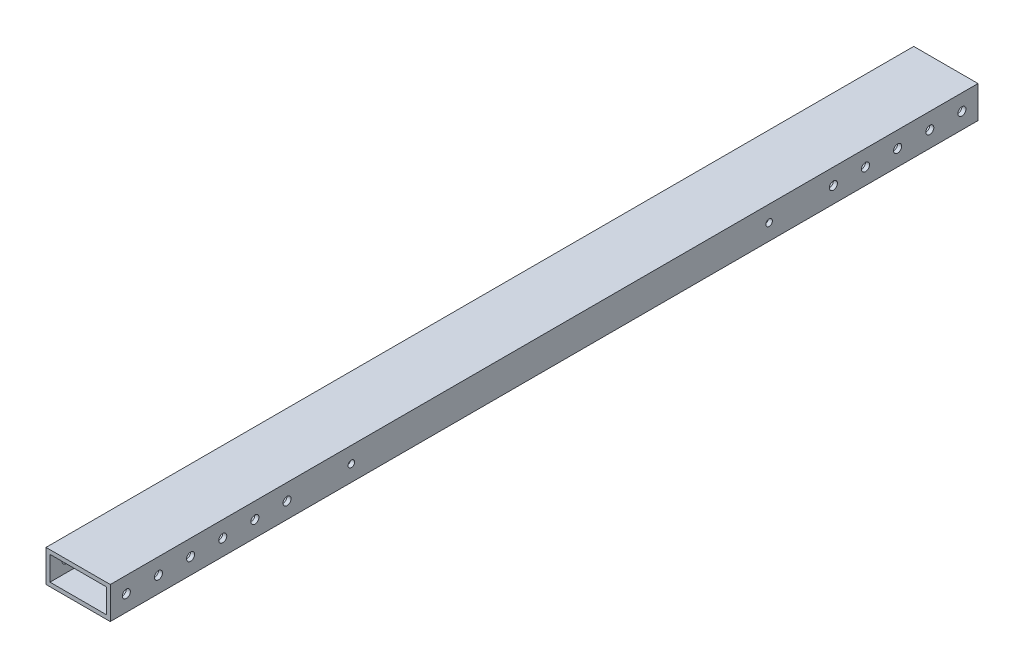
SolidWorks part; units mm, degrees
material "6061 Alloy"
ref_plane "Front Plane" through (0, 0, 0) normal (0, 0, 1) x (1, 0, 0)
ref_plane "Top Plane" through (0, 0, 0) normal (0, 1, 0) x (1, 0, 0)
ref_plane "Right Plane" through (0, 0, 0) normal (1, 0, 0) x (0, 0, -1)
sketch "Sketch1" plane through (0, 0, 0) normal (0, 0, 1) x (1, 0, 0)
  line L0 (-22.225, 9.525) -> (22.225, 9.525)
  line L2 (-25.4, 12.7) -> (25.4, 12.7)
  line L3 (-25.4, 12.7) -> (-25.4, -12.7)
  line L4 (-25.4, -12.7) -> (25.4, -12.7)
  line L5 (25.4, 12.7) -> (25.4, -12.7)
  line L10 (22.225, 9.525) -> (22.225, -9.525)
  line L11 (-22.225, -9.525) -> (22.225, -9.525)
  line L12 (-22.225, 9.525) -> (-22.225, -9.525)
  point P12 (0, 12.7)
  point P14 (25.4, 0)
  dimension "Wall Thickness" = 3.175
  dimension "Outside Width" = 50.8
  dimension "Outside Height" = 25.4
  dimension "Inside Height" = 19.05
  dimension "Inside Width" = 44.45
sketch "Sketch2" plane through (0, 0, 0) normal (1, 0, 0) x (0, 0, -1)
  line L0 (342.9, 0) -> (-342.9, 0)
  point P4 (0, 0)
  point P7 (-342.9, 0)
  point P10 (342.9, 0)
  dimension "Length" = 685.8
sketch "Sketch3" plane through (0, 0, 0) normal (0, 0, 1) x (1, 0, 0)
  line L21 (25.4, 12.7) -> (-25.4, 12.7)
  line L22 (25.4, -12.7) -> (25.4, 12.7)
  line L23 (-25.4, -12.7) -> (25.4, -12.7)
  line L24 (-25.4, 12.7) -> (-25.4, -12.7)
  line L25 (25.4, 12.7) -> (-25.4, 12.7)
  line L26 (25.4, -12.7) -> (25.4, 12.7)
  line L27 (-25.4, -12.7) -> (25.4, -12.7)
  line L28 (-25.4, 12.7) -> (-25.4, -12.7)
  line L29 (22.225, 9.525) -> (-22.225, 9.525)
  line L30 (22.225, -9.525) -> (22.225, 9.525)
  line L31 (-22.225, -9.525) -> (22.225, -9.525)
  line L32 (-22.225, 9.525) -> (-22.225, -9.525)
  line L33 (22.225, 9.525) -> (-22.225, 9.525)
  line L34 (22.225, -9.525) -> (22.225, 9.525)
  line L35 (-22.225, -9.525) -> (22.225, -9.525)
  line L36 (-22.225, 9.525) -> (-22.225, -9.525)
  dimension "D1" = 0
  dimension "D2" = 0
extrude "Boss-Extrude1" add sketch "Sketch3" along normal up to vertex (342.9 mm away) and the other way up to vertex (342.9 mm away) up to point (0, 0, 342.9) other way up to point (0, 0, -342.9)
sketch "Drawing Reference" plane through (0, 0, 0) normal (1, 0, 0) x (0, 0, -1)
  line L0 (-342.9, 0) -> (342.9, 0) construction
  line L1 (0, -12.7) -> (0, 12.7) construction
  line L2 (-342.9, -12.7) -> (342.9, -12.7) construction
  line L5 (-342.9, 12.7) -> (342.9, 12.7) construction
  point P7 (-306.324, 0)
  point P8 (306.324, 0)
  dimension "D1" = 36.576
sketch "Sketch5" plane through (25.4, 0, 0) normal (1, 0, 0) x (0, 0, -1)
  line L0 (-342.9, 0) -> (-279.4, 0)
  line L1 (-342.9, -12.7) -> (-342.9, 12.7) construction
  line L2 (-279.4, 0) -> (-254, 0)
  line L3 (-254, 0) -> (-228.6, 0)
  line L4 (-228.6, 0) -> (-203.2, 0)
sketch "Sketch8" plane through (25.4, 0, 0) normal (1, 0, 0) x (0, 0, -1)
  line L0 (342.9, 0) -> (304.8, 0)
  line L1 (342.9, -12.7) -> (342.9, 12.7) construction
  line L2 (304.8, 0) -> (279.4, 0)
  line L3 (279.4, 0) -> (254, 0)
  line L4 (254, 0) -> (228.6, 0)
  line L5 (342.9, 0) -> (330.2, 0)
hole_wizard "1/4 (0.25) Diameter Hole3" positions "Sketch12" profile "Sketch13" hole size "1/4" standard "ANSI Inch" end condition through all
sketch "Sketch12" plane through (-25.4, 0, 0) normal (-1, 0, 0) x (0, 0, 1)
  point P4 (-330.2, 0)
sketch "Sketch13" plane through (-25.4, 0, -330.2) normal (0, 1, 0) x (0, 0, 1)
  line L0 (0, 0) -> (0, 50.8)
  line L1 (0, 50.8) -> (3.175, 50.8)
  line L2 (3.175, 50.8) -> (3.175, 0)
  line L5 (3.175, 0) -> (0, 0)
  line L11 (0, -6.35) -> (0, 107.95) construction
  dimension "Thru Hole Dia." = 6.35
  dimension "Thru Hole Depth" = 50.8
hole_wizard "1/4 (0.25) Diameter Hole4" positions "Sketch14" profile "Sketch15" hole size "1/4" standard "ANSI Inch" end condition through all
sketch "Sketch14" plane through (-25.4, 0, 0) normal (-1, 0, 0) x (0, 0, 1)
  point P0 (304.8, 0)
  point P3 (330.2, 0)
sketch "Sketch15" plane through (-25.4, 0, 304.8) normal (0, 1, 0) x (0, 0, 1)
  line L0 (0, 0) -> (0, 50.8)
  line L1 (0, 50.8) -> (3.175, 50.8)
  line L2 (3.175, 50.8) -> (3.175, 0)
  line L5 (3.175, 0) -> (0, 0)
  line L11 (0, -6.35) -> (0, 107.95) construction
  dimension "Thru Hole Dia." = 6.35
  dimension "Thru Hole Depth" = 50.8
hole_wizard "1/4 (0.25) Diameter Hole5" positions "Sketch17" profile "Sketch18" hole size "1/4" standard "ANSI Inch" end condition through all
sketch "Sketch17" plane through (25.4, 0, 0) normal (1, 0, 0) x (0, 0, -1)
  point P0 (304.8, 0)
  point P3 (279.4, 0)
sketch "Sketch18" plane through (25.4, 0, -304.8) normal (0, 1, 0) x (0, 0, -1)
  line L0 (0, 0) -> (0, 50.8)
  line L1 (0, 50.8) -> (3.175, 50.8)
  line L2 (3.175, 50.8) -> (3.175, 0)
  line L5 (3.175, 0) -> (0, 0)
  line L11 (0, -6.35) -> (0, 107.95) construction
  dimension "Thru Hole Dia." = 6.35
  dimension "Thru Hole Depth" = 50.8
hole_wizard "1/4 (0.25) Diameter Hole6" positions "Sketch19" profile "Sketch20" hole size "1/4" standard "ANSI Inch" end condition through all
sketch "Sketch19" plane through (25.4, 0, 0) normal (1, 0, 0) x (0, 0, -1)
  point P0 (228.6, 0)
  point P3 (254, 0)
sketch "Sketch20" plane through (25.4, 0, -228.6) normal (0, 1, 0) x (0, 0, -1)
  line L0 (0, 0) -> (0, 50.8)
  line L1 (0, 50.8) -> (3.175, 50.8)
  line L2 (3.175, 50.8) -> (3.175, 0)
  line L5 (3.175, 0) -> (0, 0)
  line L11 (0, -6.35) -> (0, 107.95) construction
  dimension "Thru Hole Dia." = 6.35
  dimension "Thru Hole Depth" = 50.8
hole_wizard "1/4 (0.25) Diameter Hole7" positions "Sketch21" profile "Sketch22" hole size "1/4" standard "ANSI Inch" end condition through all
sketch "Sketch21" plane through (25.4, 0, 0) normal (1, 0, 0) x (0, 0, -1)
  point P0 (-203.2, 0)
  point P3 (-228.6, 0)
sketch "Sketch22" plane through (25.4, 0, 203.2) normal (0, 1, 0) x (0, 0, -1)
  line L0 (0, 0) -> (0, 50.8)
  line L1 (0, 50.8) -> (3.175, 50.8)
  line L2 (3.175, 50.8) -> (3.175, 0)
  line L5 (3.175, 0) -> (0, 0)
  line L11 (0, -6.35) -> (0, 107.95) construction
  dimension "Thru Hole Dia." = 6.35
  dimension "Thru Hole Depth" = 50.8
hole_wizard "1/4 (0.25) Diameter Hole8" positions "Sketch23" profile "Sketch24" hole size "1/4" standard "ANSI Inch" end condition through all
sketch "Sketch23" plane through (25.4, 0, 0) normal (1, 0, 0) x (0, 0, -1)
  point P0 (-279.4, 0)
  point P3 (-254, 0)
sketch "Sketch24" plane through (25.4, 0, 279.4) normal (0, 1, 0) x (0, 0, -1)
  line L0 (0, 0) -> (0, 50.8)
  line L1 (0, 50.8) -> (3.175, 50.8)
  line L2 (3.175, 50.8) -> (3.175, 0)
  line L5 (3.175, 0) -> (0, 0)
  line L11 (0, -6.35) -> (0, 107.95) construction
  dimension "Thru Hole Dia." = 6.35
  dimension "Thru Hole Depth" = 50.8
sketch "Sketch25" plane through (25.4, 0, 0) normal (1, 0, 0) x (0, 0, -1)
  line L0 (-203.2, 0) -> (-152.4, 0)
  line L1 (228.6, 0) -> (177.8, 0)
hole_wizard "13/64 (0.20313) Diameter Hole1" positions "Sketch26" profile "Sketch27" hole size "13/64" standard "ANSI Inch" end condition through all
sketch "Sketch26" plane through (25.4, 0, 0) normal (1, 0, 0) x (0, 0, -1)
  point P0 (-152.4, 0)
  point P3 (177.8, 0)
sketch "Sketch27" plane through (25.4, 0, 152.4) normal (0, 1, 0) x (0, 0, -1)
  line L0 (0, 0) -> (0, 50.8)
  line L1 (0, 50.8) -> (2.5798, 50.8)
  line L2 (2.5798, 50.8) -> (2.5798, 0)
  line L5 (2.5798, 0) -> (0, 0)
  line L11 (0, -6.35) -> (0, 107.95) construction
  dimension "Thru Hole Dia." = 5.1595
  dimension "Thru Hole Depth" = 50.8
sketch "Sketch30" plane through (-25.4, 0, 0) normal (-1, 0, 0) x (0, 0, 1)
  point P0 (-128.9434, 0.355)
  point P1 (-103.5434, 0.3445)
  point P2 (77.4316, 0.355)
  point P3 (102.8316, 0.355)
hole_wizard "1/2 (0.5) Diameter Hole1" positions "Sketch33" profile "Sketch34" hole size "1/2" standard "ANSI Inch"
sketch "Sketch33" plane through (-25.4, 0, 0) normal (-1, 0, 0) x (0, 0, 1)
  point P0 (-128.9434, 0.355)
  point P3 (-103.5434, 0.3445)
  point P7 (77.4316, 0.355)
  point P10 (102.8316, 0.355)
sketch "Sketch34" plane through (-25.4, 0.355, -128.9434) normal (0, 1, 0) x (0, 0, 1)
  line L0 (0, 0) -> (0, 10.1655)
  line L1 (0, 10.1655) -> (6.35, 6.35)
  line L2 (6.35, 6.35) -> (6.35, 0)
  line L5 (6.35, 0) -> (0, 0)
  line L10 (0, 10.1655) -> (-6.35, 6.35) construction
  line L11 (0, -6.35) -> (0, 107.95) construction
  dimension "Hole Dia." = 12.7
  dimension "Hole Depth" = 6.35
  dimension "Drill Angle" = 118
equation "\"D1@Drawing Reference\"=\"Outside Width@Sketch1\" * 0.72"
